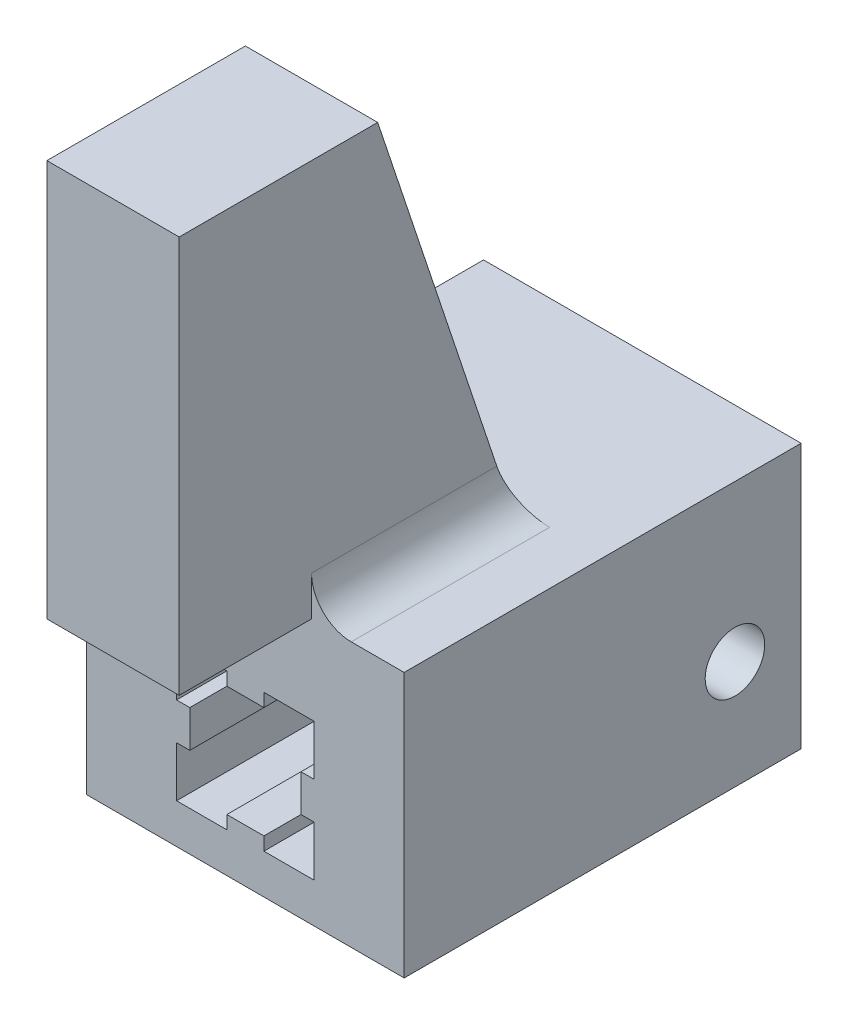
SolidWorks part; units mm, degrees
ref_plane "Front Plane" through (0, 0, 0) normal (0, 0, 1) x (1, 0, 0)
ref_plane "Top Plane" through (0, 0, 0) normal (0, 1, 0) x (1, 0, 0)
ref_plane "Right Plane" through (0, 0, 0) normal (1, 0, 0) x (0, 0, -1)
sketch "Esquisse1" plane through (0, 0, 0) normal (0, 0, 1) x (1, 0, 0)
  line L1 (-12, 10) -> (12, 10)
  line L2 (-12, 10) -> (-12, -10)
  line L3 (-12, -10) -> (12, -10)
  line L4 (12, 10) -> (12, -10)
  point P4 (0, -10)
  point P5 (-12, 0)
  dimension "D1" = 24
  dimension "D2" = 20
extrude "Main Extrusion" add sketch "Esquisse1" along normal blind 30
sketch "Esquisse3" plane through (0, 0, 0) normal (0, 0, -1) x (-1, 0, 0)
  line L0 (-5.2, 3.4) -> (-5.2, -0.4)
  line L1 (-5.2, -0.4) -> (-4.2, -0.4)
  line L2 (-4.2, -0.4) -> (-4.2, -3.2)
  line L3 (-4.2, -3.2) -> (-5.2, -3.2)
  line L4 (-5.2, -3.2) -> (-5.2, -7)
  line L5 (-5.2, -7) -> (-1.4, -7)
  line L6 (-1.4, -7) -> (-1.4, -6)
  line L7 (-1.4, -6) -> (1.4, -6)
  line L8 (1.4, -6) -> (1.4, -7)
  line L9 (1.4, -7) -> (5.2, -7)
  line L10 (5.2, -7) -> (5.2, -3.2)
  line L11 (5.2, -3.2) -> (4.2, -3.2)
  line L12 (4.2, -3.2) -> (4.2, -0.4)
  line L13 (4.2, -0.4) -> (5.2, -0.4)
  line L14 (5.2, -0.4) -> (5.2, 3.4)
  line L15 (5.2, 3.4) -> (1.4, 3.4)
  line L16 (1.4, 3.4) -> (1.4, 2.4)
  line L17 (1.4, 2.4) -> (-1.4, 2.4)
  line L18 (-1.4, 2.4) -> (-1.4, 3.4)
  line L19 (-1.4, 3.4) -> (-5.2, 3.4)
  line L21 (12, -10) -> (-12, -10) construction
  point P20 (0, -6)
  point P24 (0, -10)
  dimension "D1" = 2.8
  dimension "D2" = 10.4
  dimension "D3" = 1
  dimension "D4" = 1
  dimension "D5" = 3
extrude "Main Riding Hole" cut sketch "Esquisse3" against normal through all
sketch "Esquisse4" plane through (-12, 0, 0) normal (-1, 0, 0) x (0, 0, 1)
  line L1 (0, -3.2) -> (0, -0.4) construction
  line L2 (0, 10) -> (0, -10) construction
  circle A0 centre (5, -1.8) radius 2.25
  point P5 (0, -1.8)
  dimension "D1" = 4.5
  dimension "D2" = 5
extrude "TractorHole" cut sketch "Esquisse4" against normal blind 8
mirror "TractorHoleSymetry" about plane through (0, 0, 0) normal (1, 0, 0) of "TractorHole"
sketch "Esquisse5" plane through (0, 0, 0) normal (1, 0, 0) x (0, 0, -1)
  line L0 (-40, 10) -> (-40, 40)
  line L1 (-30, 10) -> (0, 10) construction
  line L2 (-40, 40) -> (-25, 40)
  line L3 (-25, 40) -> (-15, 10)
  line L4 (-15, 10) -> (-40, 10)
  line L6 (-30, -10) -> (-30, 10) construction
  point P4 (-43.5297, 10)
  dimension "D1" = 30
  dimension "D2" = 15
  dimension "D3" = 25
  dimension "D4" = 10
extrude "ImpactPiece" add sketch "Esquisse5" against normal mid plane 10
fillet "Congé1" radius 3 2 edges at (-5, 10, 22.5) (5, 10, 22.5)
